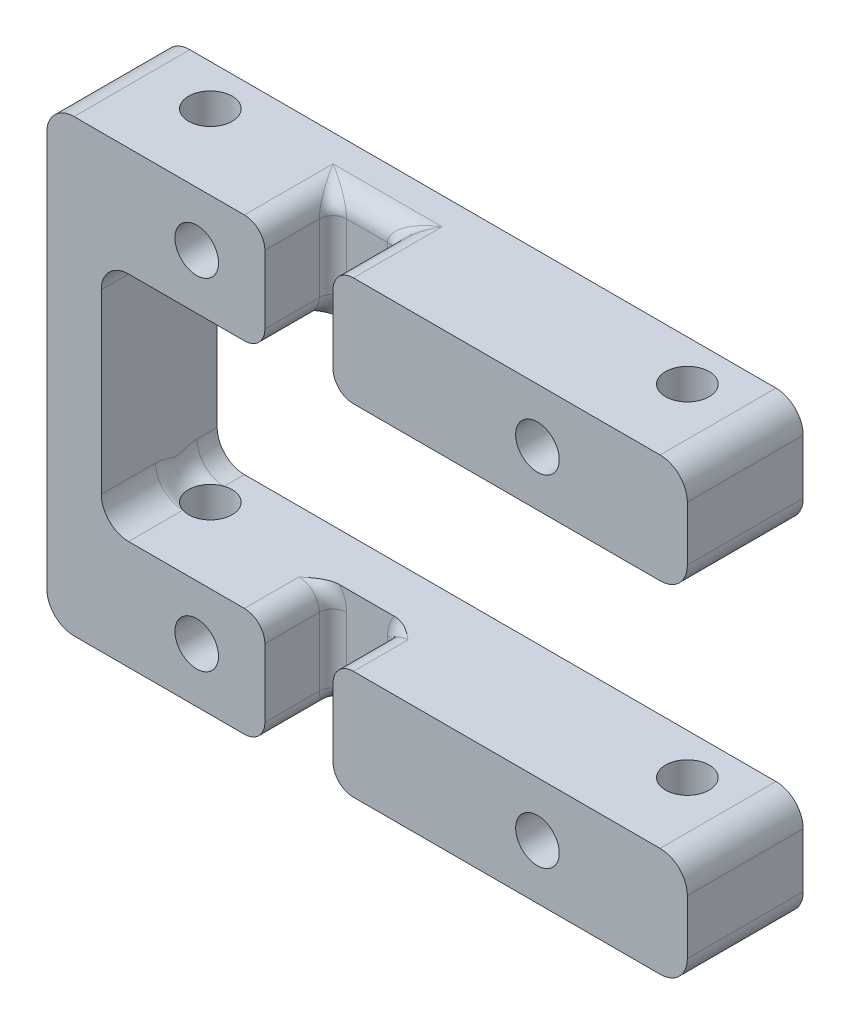
SolidWorks part; units mm, degrees
material "6061 合金"
ref_plane "前视基准面" through (0, 0, 0) normal (0, 0, 1) x (1, 0, 0)
ref_plane "上视基准面" through (0, 0, 0) normal (0, 1, 0) x (1, 0, 0)
ref_plane "右视基准面" through (0, 0, 0) normal (1, 0, 0) x (0, 0, -1)
other "Configuration Table"
sketch "草图1" plane through (0, 0, 0) normal (0, 0, 1) x (1, 0, 0)
  line L1 (0, 0) -> (47, 0)
  line L2 (0, 0) -> (0, 33)
  line L3 (0, 33) -> (47, 33)
  line L4 (47, 0) -> (47, 33)
  line L5 (0, 16.5) -> (47, 16.5) construction
  circle A0 centre (11, 29) radius 1.6
  circle A1 centre (36, 29) radius 1.6
  circle A2 centre (36, 4) radius 1.6
  circle A3 centre (11, 4) radius 1.6
  dimension "D3" = 3.2
  dimension "D4" = 11
  dimension "D6" = 25
  dimension "D1" = 47
  dimension "D2" = 33
  dimension "D5" = 12.5
extrude "凸台-拉伸1" add sketch "草图1" along normal blind 8.5
ref_plane "基准面1" through (0, 16.5, 0) normal (0, -1, 0) x (-1, 0, 0)
sketch "草图6" plane through (0, 0, 8.5) normal (0, 0, 1) x (1, 0, 0)
  line L0 (47, 0) -> (47, 33) construction
  line L1 (-3.3, 16.5) -> (3.3, 16.5) construction
  line L2 (4, 25) -> (47, 25)
  line L3 (4, 25) -> (4, 8)
  line L4 (4, 8) -> (47, 8)
  line L5 (47, 25) -> (47, 8)
  line L6 (0, 16.5) -> (67.0038, 16.5) construction
  line L7 (0, 33) -> (0, 0) construction
  line L8 (67.0038, 16.5) -> (65.3019, 16.5) construction
  line L12 (37, 9.5) -> (25, 9.5) construction
  line L13 (0, 23.5) -> (12, 23.5) construction
  line L14 (0, 23.5) -> (0, 9.5) construction
  line L15 (0, 9.5) -> (12, 9.5) construction
  line L16 (12, 23.5) -> (12, 9.5) construction
  line L18 (37, 23.5) -> (25, 23.5) construction
  line L19 (37, 23.5) -> (37, 9.5) construction
  dimension "D1" = 17
  dimension "D2" = 4
  dimension "D3" = 12
  dimension "D4" = 14
extrude "切除-拉伸1" cut sketch "草图6" against normal blind 10
sketch "草图7" plane through (0, 0, 0) normal (0, -1, 0) x (1, 0, 0)
  line L0 (0, 8.5) -> (47, 8.5) construction
  line L1 (16, 8.5) -> (21, 8.5)
  line L2 (16, 8.5) -> (16, 3.5)
  line L3 (16, 3.5) -> (21, 3.5)
  line L4 (21, 8.5) -> (21, 3.5)
  dimension "D1" = 5
  dimension "D2" = 5
  dimension "D3" = 16
extrude "切除-拉伸2" cut sketch "草图7" against normal through all
sketch "草图8" plane through (0, 0, 0) normal (0, -1, 0) x (1, 0, 0)
  line L0 (0, 0) -> (47, 0) construction
  line L1 (0, 8.5) -> (0, 0) construction
  circle A0 centre (6.5, 3) radius 1.6
  circle A1 centre (41.5, 3) radius 1.6
  dimension "D1" = 3.2
  dimension "D2" = 35
  dimension "D3" = 3
  dimension "D4" = 6.5
extrude "切除-拉伸3" cut sketch "草图8" against normal through all
fillet "圆角1" radius 1.5 10 edges at (21, 33, 6) (21, 0, 6) (21, 25, 6) (21, 8, 6) (18.5, 33, 3.5) (18.5, 0, 3.5) (16, 33, 6) (16, 0, 6) (16, 25, 6) (16, 8, 6)
fillet "圆角2" radius 2 8 edges at (47, 33, 4.25) (47, 25, 4.25) (47, 8, 4.25) (47, 0, 4.25) (4, 8, 4.25) (4, 25, 4.25) (0, 33, 4.25) (0, 0, 4.25)
fillet "圆角3" radius 1 12 edges at (21.4393, 32.5607, 3.0607) (21.4393, 25.4393, 3.5) (15.5607, 32.5607, 3.0607) (15.5607, 25.4393, 3.5) (15.5607, 7.5607, 3.5) (15.5607, 0.4393, 3.0607) (21.4393, 7.5607, 3.5) (21, 4, 3.5) (21, 29, 3.5) (16, 29, 3.5) (16, 4, 3.5) (21.4393, 0.4393, 3.0607)
